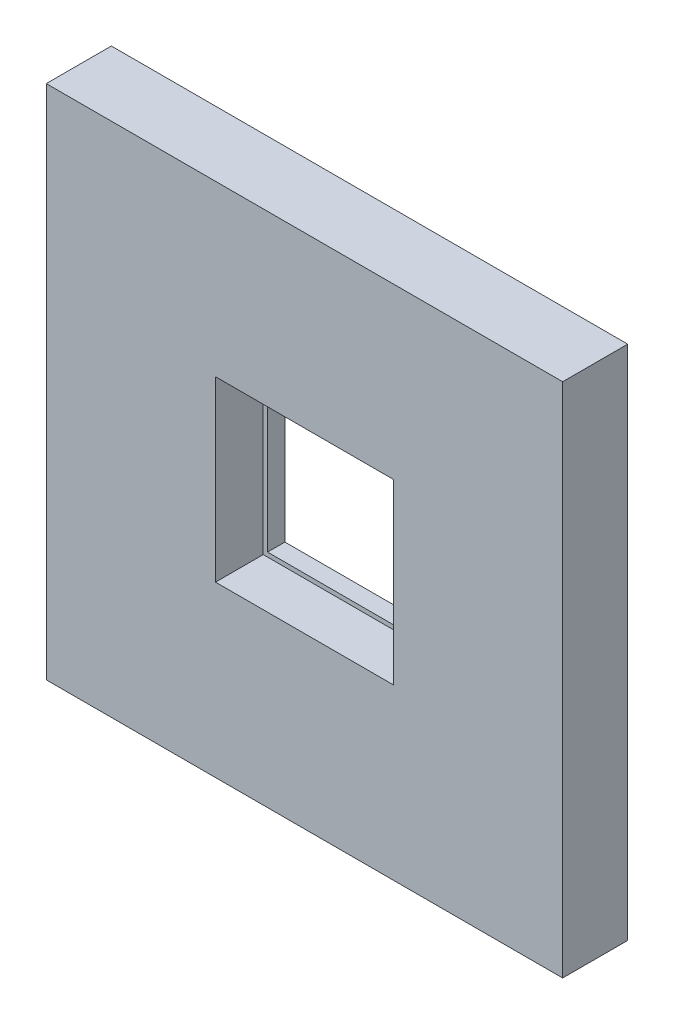
SolidWorks part; units mm, degrees
ref_plane "Front Plane" through (0, 0, 0) normal (0, 0, 1) x (1, 0, 0)
ref_plane "Top Plane" through (0, 0, 0) normal (0, 1, 0) x (1, 0, 0)
ref_plane "Right Plane" through (0, 0, 0) normal (1, 0, 0) x (0, 0, -1)
sketch "Sketch1" plane through (0, 0, 0) normal (0, 0, 1) x (1, 0, 0)
  line L5 (-1.95, -1.95) -> (1.95, -1.95)
  line L6 (-1.95, -1.95) -> (-1.95, 1.95)
  line L11 (-1.95, 1.95) -> (1.95, 1.95)
  line L12 (1.95, -1.95) -> (1.95, 1.95)
  line L13 (-1.95, -1.95) -> (1.95, 1.95) construction
  line L14 (-1.95, 1.95) -> (1.95, -1.95) construction
  line L23 (-5.95, -5.95) -> (-5.95, 5.95)
  line L24 (-5.95, 5.95) -> (5.95, 5.95)
  line L28 (-2.05, -2.05) -> (-2.05, 2.05)
  line L29 (-2.05, 2.05) -> (2.05, 2.05)
  line L30 (2.05, -2.05) -> (2.05, 2.05)
  line L31 (-2.05, -2.05) -> (2.05, -2.05)
  line L36 (5.95, -5.95) -> (5.95, 5.95)
  line L37 (-5.95, -5.95) -> (5.95, -5.95)
  point P0 (0, 0)
  point P10 (0, 0)
  dimension "D1" = 3.9
  dimension "D2" = 3.9
  dimension "D3" = 0.1
  dimension "D4" = 4
extrude "Boss-Extrude1" add sketch "Sketch1" along normal blind 1.5 contours L23 L37 L36 L24 L31 L28 L29 L30 region at (-5.7817, 0, 0)
extrude "Boss-Extrude2" add sketch "Sketch1<6>" along normal blind 0.4 separate body contours L28 L31 L30 L29 L12 L5 L6 L11 region at (-1.992, 0, 0)
sketch "Sketch1<6>" plane through (0, 0, 0) normal (0, 0, 1) x (1, 0, 0) same geometry as "Sketch1"
